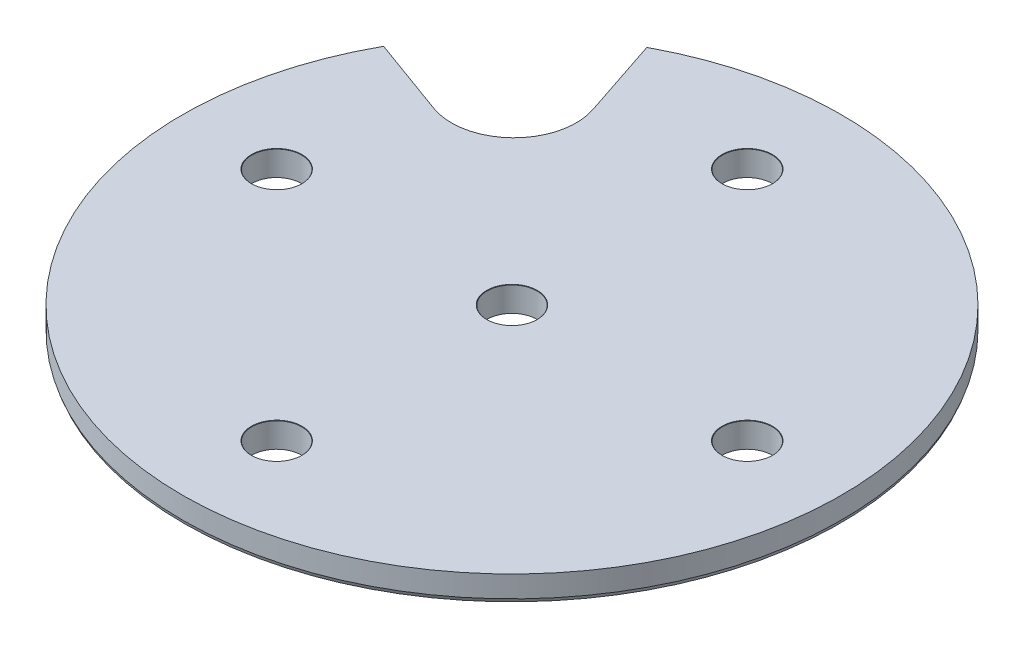
SolidWorks part; units mm, degrees
ref_plane "Front Plane" through (0, 0, 0) normal (0, 0, 1) x (1, 0, 0)
ref_plane "Top Plane" through (0, 0, 0) normal (0, 1, 0) x (1, 0, 0)
ref_plane "Right Plane" through (0, 0, 0) normal (1, 0, 0) x (0, 0, -1)
sketch "Sketch1" plane through (0, 0, 0) normal (0, 1, 0) x (1, 0, 0)
  circle A0 centre (0, 0) radius 26.4
  dimension "D1" = 52.8
extrude "Boss-Extrude1" add sketch "Sketch1" along normal blind 2 contours A0
sketch "Sketch2" plane through (0, 2, 0) normal (0, 1, 0) x (1, 0, 0)
  circle A0 centre (0, 0) radius 21.8
  circle A1 centre (-18.85, 0) radius 2.95 construction
  circle A2 centre (0, 18.85) radius 2.95 construction
  circle A3 centre (18.85, 0) radius 2.95 construction
  circle A4 centre (0, -18.85) radius 2.95 construction
  point P3 (-18.85, 0)
  point P8 (0, 18.85)
  point P10 (18.85, 0)
  point P12 (0, -18.85)
  point P14 (0, 0)
  dimension "D1" = 43.6
  dimension "D2" = 5.9
  dimension "D3" = 4
hole_wizard "Ø4.0 (4) Diameter Hole1" positions "Sketch2" profile "Sketch4" hole size "Ø4.0" standard "ANSI Metric" end condition through all
sketch "Sketch4" plane through (0, 2, 0) normal (1, 0, 0) x (0, 0, 1)
  line L0 (0, 0) -> (0, 2)
  line L1 (0, 2) -> (2, 2)
  line L2 (2, 2) -> (2, 0.0273)
  line L3 (2, 0.0273) -> (2.025, 0)
  line L5 (2.025, 0) -> (0, 0)
  line L6 (-2, 0.0273) -> (-2.025, 0) construction
  line L11 (0, -6.35) -> (0, 107.95) construction
  dimension "Thru Hole Dia." = 4
  dimension "Thru Hole Depth" = 2
  dimension "Near C'Sink Dia." = 4.05
  dimension "Near C'Sink Angle" = 85
chamfer "Chamfer1" distance 0.1 angle 70 1 edges at (0, 0, 26.4) first distance on face at (-18.85, 0, 2)
sketch "Sketch5" plane through (0, 2, 0) normal (0, 1, 0) x (1, 0, 0)
  line L0 (-23.0864, 12.8054) -> (-7.0554, 6.9802)
  line L1 (-7.0554, 6.9802) -> (-12.4661, 23.2714)
  circle A0 centre (0, 0) radius 26.4 construction
  circle A1 centre (-15.0564, 15.2074) radius 5
  circle M9 centre (0, 0) radius 26.4
  dimension "D1" = 10
extrude "Cut-Extrude1" cut sketch "Sketch5" against normal through all contours A1 | A1 L0 M9 | A1 L1 M9 region at (-20.6996, 2, -13.745) region at (-15.0564, 2, -15.2074) region at (-13.4772, 2, -20.845)
